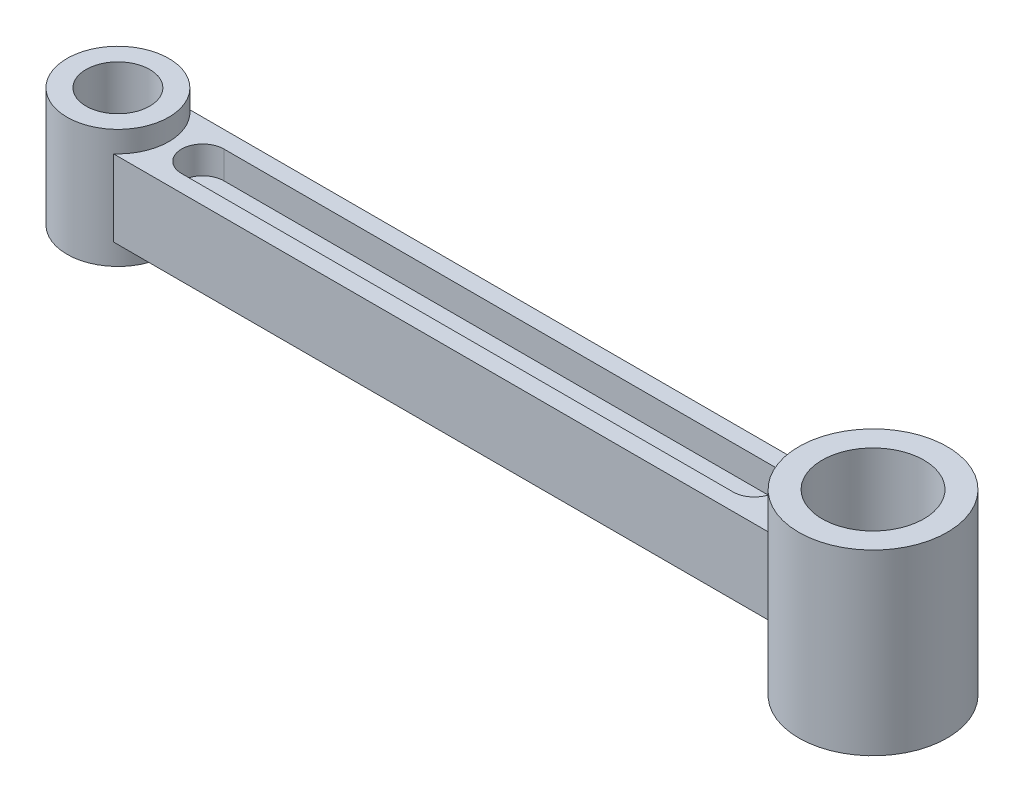
SolidWorks part; units mm, degrees
ref_plane "Front Plane" through (0, 0, 0) normal (0, 0, 1) x (1, 0, 0)
ref_plane "Top Plane" through (0, 0, 0) normal (0, 1, 0) x (1, 0, 0)
ref_plane "Right Plane" through (0, 0, 0) normal (1, 0, 0) x (0, 0, -1)
sketch "Sketch1" plane through (0, 0, 0) normal (0, 1, 0) x (1, 0, 0)
  line L0 (0, 0) -> (178, 0) construction
  line L1 (7.9373, 9) -> (162.9917, 9)
  line L2 (7.9373, -9) -> (162.9917, -9)
  line L3 (150, 5) -> (20, 5)
  line L4 (20, -5) -> (150, -5)
  circle A0 centre (0, 0) radius 7.5
  circle A1 centre (0, 0) radius 12
  circle A2 centre (178, 0) radius 12
  circle A3 centre (178, 0) radius 17.5
  arc A4 (20, 5) -> (20, -5) centre (20, 0) ccw
  arc A5 (150, -5) -> (150, 5) centre (150, 0) ccw
  dimension "D1" = 15
  dimension "D2" = 24
  dimension "D4" = 24
  dimension "D5" = 35
  dimension "D8" = 28
  dimension "D3" = 178
  dimension "D6" = 18
  dimension "D7" = 10
  dimension "D9" = 130
extrude "Boss-Extrude1" add sketch "Sketch1" along normal mid plane 28 contours A0 A1 region at (10.6279, 0, -4.7976)
extrude "Boss-Extrude2" add sketch "Sketch1<3>" along normal mid plane 42 separate body contours A3 A2 region at (182.5372, 0, -16.3886)
sketch "Sketch1<3>" plane through (0, 0, 0) normal (0, 1, 0) x (1, 0, 0) same geometry as "Sketch1"
extrude "Boss-Extrude3" add sketch "Sketch1<4>" along normal mid plane 18 contours A1 L0 A4 L3 A5 A3 L1 | L0 A1 L2 A3 A5 L4 A4 region at (87.0893, 0, -6.6573) region at (87.0893, 0, 6.6573)
sketch "Sketch1<4>" plane through (0, 0, 0) normal (0, 1, 0) x (1, 0, 0) same geometry as "Sketch1"
extrude "Boss-Extrude4" add sketch "Sketch1<5>" along normal mid plane 5 contours A4 L0 A5 L3 | L0 A4 L4 A5 region at (85, 0, -2.4785) region at (85, 0, 2.4785)
sketch "Sketch1<5>" plane through (0, 0, 0) normal (0, 1, 0) x (1, 0, 0) same geometry as "Sketch1"
